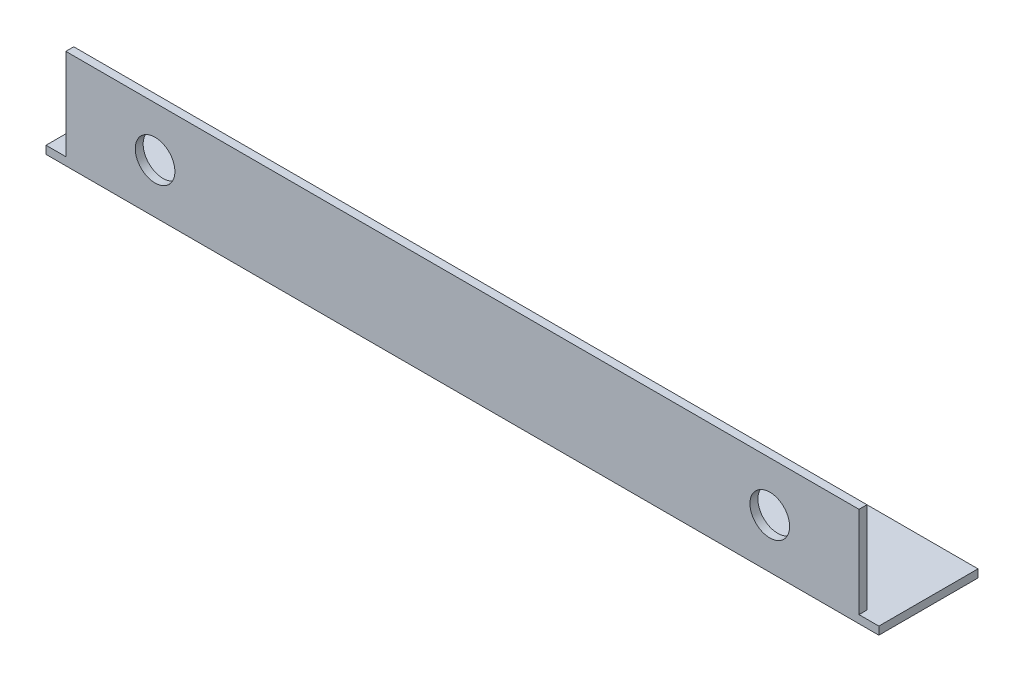
SolidWorks part; units mm, degrees
ref_plane "Спереди" through (0, 0, 0) normal (0, 0, 1) x (1, 0, 0)
ref_plane "Сверху" through (0, 0, 0) normal (0, 1, 0) x (1, 0, 0)
ref_plane "Справа" through (0, 0, 0) normal (1, 0, 0) x (0, 0, -1)
sketch "Эскиз1" plane through (0, 0, 0) normal (1, 0, 0) x (0, 0, -1)
  line L0 (0, 25) -> (0, 0)
  line L1 (0, 0) -> (25, 0)
extrude "Вытянуть-Тонкостенный1" add sketch "Эскиз1" along normal blind 210 thin thin type one direction reverse wall 2
sketch "Эскиз2" plane through (0, 0, 0) normal (0, 0, 1) x (1, 0, 0)
  line L0 (105, 0) -> (105, -9.5468) construction
  line L1 (210, 0) -> (0, 0) construction
  line L2 (205, 25) -> (205, 2)
  line L3 (0, 25) -> (5, 25)
  line L4 (0, 25) -> (0, 2)
  line L5 (0, 2) -> (5, 2)
  line L6 (5, 25) -> (5, 2)
  line L7 (210, 2) -> (205, 2)
  line L8 (210, 25) -> (210, 2)
  line L9 (210, 25) -> (205, 25)
  circle A0 centre (27.5, 12.5) radius 5
  circle A1 centre (182.5, 12.5) radius 5
  dimension "D1" = 77.5
  dimension "D2" = 5
extrude "Вырез-Вытянуть1" cut sketch "Эскиз2" against normal through all
